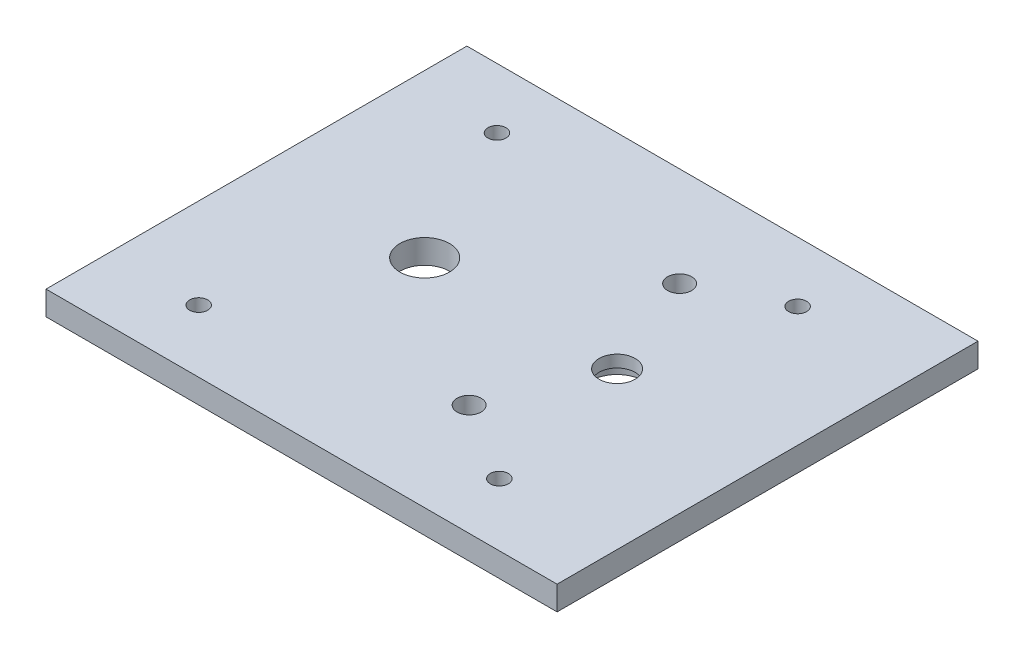
SolidWorks part; units mm, degrees
ref_plane "Front Plane" through (0, 0, 0) normal (0, 0, 1) x (1, 0, 0)
ref_plane "Top Plane" through (0, 0, 0) normal (0, 1, 0) x (1, 0, 0)
ref_plane "Right Plane" through (0, 0, 0) normal (1, 0, 0) x (0, 0, -1)
sketch "Sketch1" plane through (0, 0, 0) normal (0, 1, 0) x (1, 0, 0)
  line L0 (0, 8.2993) -> (0, -7.906) construction
  line L1 (-42.5, 35) -> (42.5, 35)
  line L2 (-42.5, 35) -> (-42.5, -35)
  line L3 (-42.5, -35) -> (42.5, -35)
  line L4 (42.5, 35) -> (42.5, -35)
  line L5 (-42.5, 35) -> (42.5, -35) construction
  line L6 (-42.5, -35) -> (42.5, 35) construction
  line L7 (-12.4915, 0.1967) -> (14.4413, 0.1967) construction
  line L8 (9.5, 1) -> (10.7497, 1) construction
  line L9 (37.5085, 0.1967) -> (64.4413, 0.1967) construction
  line L11 (15.0001, 2.9838) -> (15.0001, -1.0162)
  line L13 (17.9999, 3.0162) -> (17.9999, -0.9838)
  line L14 (15.0001, 2.9838) -> (17.9999, -0.9838) construction
  line L15 (15.0001, -1.0162) -> (17.9999, 3.0162) construction
  circle A0 centre (-27.5, 25) radius 1.5
  circle A1 centre (22.5, 25) radius 1.5
  circle A2 centre (22.5, -24.6067) radius 1.5
  circle A3 centre (-27.5, -24.6067) radius 1.5
  circle A4 centre (16.5, 1) radius 10
  circle A5 centre (-15.52, 1) radius 20
  arc A6 (15.0001, 2.9838) -> (17.9999, 3.0162) centre (16.5217, 1.0001) cw
  arc A7 (15.0001, -1.0162) -> (17.9999, -0.9838) centre (16.4783, 0.9999) ccw
  circle A8 centre (16.4783, 0.9999) radius 4.5
  circle A12 centre (-15.52, 1) radius 4.125
  circle A13 centre (16.4783, 0.9999) radius 3
  circle A14 centre (9.5, 1) radius 14
  circle A17 centre (85.0307, -10.8481) radius 14
  circle A18 centre (86.1334, -28.3481) radius 2
  circle A19 centre (86.1334, 6.6519) radius 2
  circle A20 centre (9.5, 1) radius 14
  circle A21 centre (9.4072, 18.471) radius 2
  circle A22 centre (9.4014, -16.529) radius 2
  point P0 (0, 0)
  dimension "D3" = 15
  dimension "D6" = 3
  dimension "D7" = 26
  dimension "D10" = 32.02
  dimension "D11" = 9
  dimension "D12" = 7
  dimension "D15" = 1.1027
  dimension "D17" = 1.1027
  dimension "D20" = 8.25
  dimension "D21" = 6
  dimension "D1" = 85
  dimension "D2" = 70
  dimension "D4" = 10
  dimension "D8" = 4
  dimension "D9" = 3
  dimension "D18" = 36
  dimension "D19" = 4
  dimension "D22" = 28.9915
  dimension "D5" = 2
extrude "Boss-Extrude4" add sketch "Sketch1" along normal blind 4 contours L4 L1 L2 L3 A14 A4 A5 A2 A1 A0 A3 | A14 A5 | A14 A4 | A5 A14 A4 | A5 A14 | A4 A14 A8 | A8 A13 | A4 A14 A5 region at (0, 0, -33.8989) region at (23.9705, 0, -1) region at (22.3127, 0, -5.9551) region at (6.1628, 0, -1) region at (-5.0421, 0, -1) region at (0.1582, 0, -1) region at (12.1056, 0, -0.9999)
sketch "Sketch2" plane through (0, 4, 0) normal (0, 1, 0) x (1, 0, 0)
  circle A3 centre (-15.52, 1) radius 9.125
  circle A4 centre (-15.52, 1) radius 9.125
  dimension "D1" = 5
extrude "Cut-Extrude2" cut sketch "Sketch1<7>" along normal blind 2 contours A8
sketch "Sketch1<7>" plane through (0, 0, 0) normal (0, 1, 0) x (1, 0, 0) same geometry as "Sketch1"
